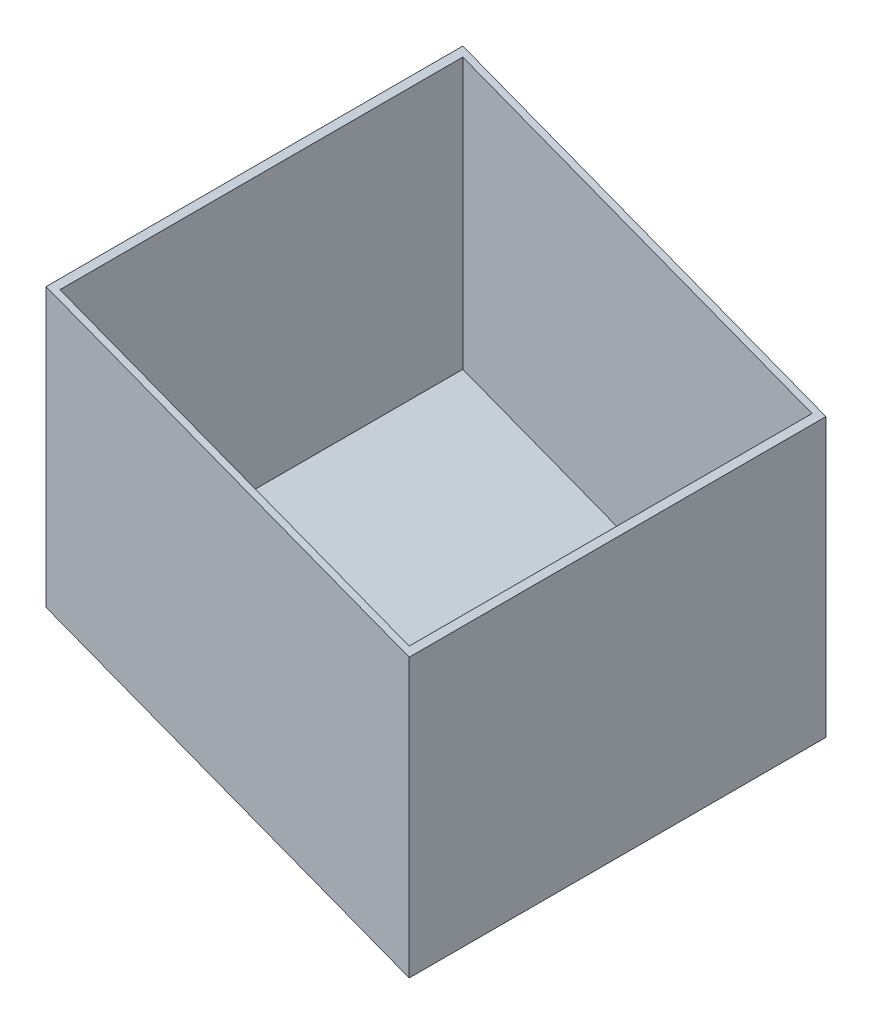
SolidWorks part; units mm, degrees
ref_plane "Front Plane" through (0, 0, 0) normal (0, 0, 1) x (1, 0, 0)
ref_plane "Top Plane" through (0, 0, 0) normal (0, 1, 0) x (1, 0, 0)
ref_plane "Right Plane" through (0, 0, 0) normal (1, 0, 0) x (0, 0, -1)
sketch "Sketch1" plane through (0, 0, 0) normal (0, 0, 1) x (1, 0, 0)
  line L0 (-33.1981, 25.4) -> (-33.1981, -25.4)
  line L1 (-33.1981, -25.4) -> (33.1981, -50.8871)
  line L2 (33.1981, -50.8871) -> (33.1981, -0.0871)
  line L3 (33.1981, -0.0871) -> (-33.1981, 25.4)
  point P4 (0, -38.1436)
  point P6 (-33.1981, 0)
  dimension "D1" = 50.8
  dimension "D2" = 71.12
  dimension "D3" = 69
extrude "Boss-Extrude1" add sketch "Sketch1" along normal mid plane 76.2
shell "Shell1" thickness 1.27 removed face at (0, 12.6564, 0)
